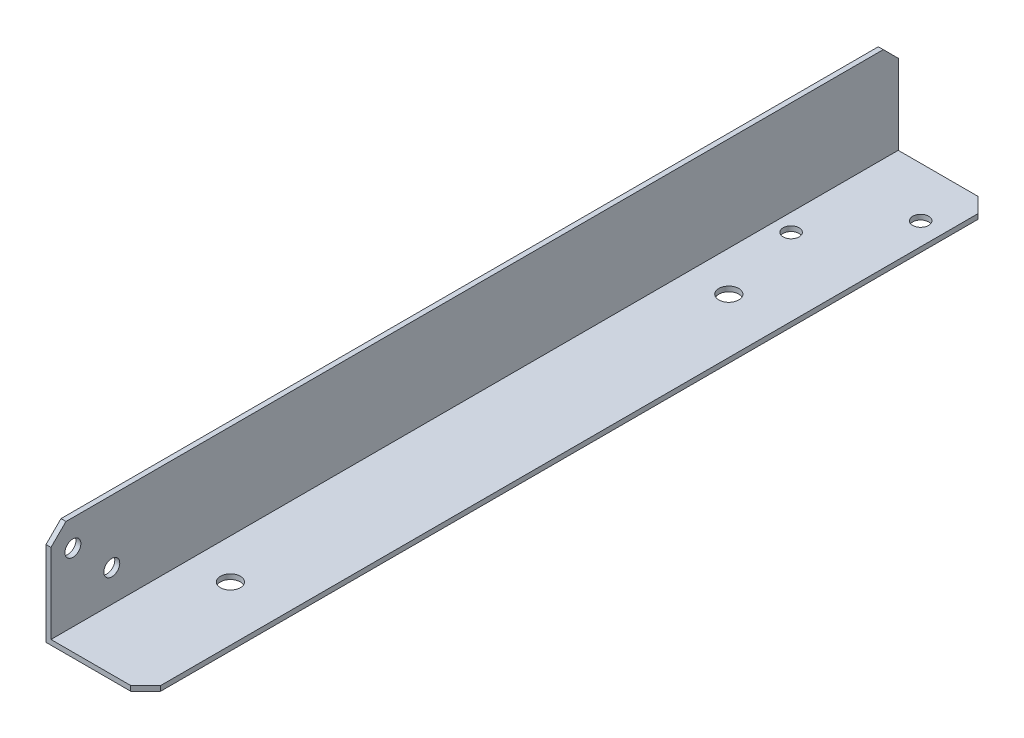
SolidWorks part; units mm, degrees
material "6063-T5"
ref_plane "Спереди" through (0, 0, 0) normal (0, 0, 1) x (1, 0, 0)
ref_plane "Сверху" through (0, 0, 0) normal (0, 1, 0) x (1, 0, 0)
ref_plane "Справа" through (0, 0, 0) normal (1, 0, 0) x (0, 0, -1)
sketch "Sketch1" plane through (0, 0, 0) normal (0, 0, 1) x (1, 0, 0)
  line L0 (0, 0) -> (20, 0)
  line L1 (20, 0) -> (20, 1)
  line L2 (20, 1) -> (1, 1)
  line L3 (1, 1) -> (1, 20)
  line L4 (1, 20) -> (0, 20)
  line L5 (0, 20) -> (0, 0)
  dimension "D1" = 20
  dimension "D2" = 20
  dimension "D3" = 1
  dimension "D4" = 1
extrude "Base" add sketch "Sketch1" along normal blind 170
chamfer "Chamfer1" distance 3 angle 45 4 edges at (20, 0.5, 170) (0.5, 20, 170) (0.5, 20, 0) (20, 0.5, 0)
hole_wizard "Ø4.0 (4) Cable tie Holes" positions "Sketch8" profile "Sketch9" hole size "Ø4.0" standard "ANSI Metric" end condition through all
sketch "Sketch8" plane through (0, 1, 0) normal (0, 1, 0) x (1, 0, 0)
  line L0 (0, -167) -> (0, -3) construction
  line L1 (17, 0) -> (1, 0) construction
  point P0 (9, -42)
  point P2 (9, -142)
  dimension "D1" = 9
  dimension "D2" = 42
  dimension "D3" = 142
sketch "Sketch9" plane through (9, 1, 42) normal (1, 0, 0) x (0, 0, 1)
  line L0 (0, 0) -> (0, 1)
  line L1 (0, 1) -> (2, 1)
  line L2 (2, 1) -> (2, 0)
  line L5 (2, 0) -> (0, 0)
  line L11 (0, -6.35) -> (0, 107.95) construction
  dimension "Thru Hole Dia." = 4
  dimension "Thru Hole Depth" = 1
hole_wizard "Ø3.1 (3.1) CableChainSideHoles" positions "Sketch10" profile "Sketch11" hole size "Ø3.2" standard "ANSI Metric" end condition through all
sketch "Sketch10" plane through (1, 0, 0) normal (1, 0, 0) x (0, 0, -1)
  line L0 (-167, 0) -> (-3, 0) construction
  line L1 (-170, 1) -> (-170, 17) construction
  point P0 (-165.6, 14.68)
  point P2 (-157.8, 7.38)
  dimension "D1" = 7.3
  dimension "D2" = 7.8
  dimension "D3" = 7.38
  dimension "D4" = 4.4
sketch "Sketch11" plane through (1, 14.68, 165.6) normal (0, 1, 0) x (0, 0, -1)
  line L0 (0, 0) -> (0, 1)
  line L1 (0, 1) -> (1.6, 1)
  line L2 (1.6, 1) -> (1.6, 0)
  line L5 (1.6, 0) -> (0, 0)
  line L11 (0, -6.35) -> (0, 107.95) construction
  dimension "Thru Hole Dia." = 3.2
  dimension "Thru Hole Depth" = 1
hole_wizard "Ø3.2 (3.2) CarriageSide" positions "Sketch12" profile "Sketch13" hole size "Ø3.2" standard "ANSI Metric" end condition through all
sketch "Sketch12" plane through (0, 1, 0) normal (0, 1, 0) x (1, 0, 0)
  line L0 (0, -167) -> (0, -3) construction
  line L1 (17, 0) -> (1, 0) construction
  point P0 (15.5, -10)
  point P2 (4.5, -25)
  dimension "D1" = 4.5
  dimension "D2" = 15
  dimension "D3" = 10
  dimension "D4" = 11
sketch "Sketch13" plane through (15.5, 1, 10) normal (1, 0, 0) x (0, 0, 1)
  line L0 (0, 0) -> (0, 1)
  line L1 (0, 1) -> (1.6, 1)
  line L2 (1.6, 1) -> (1.6, 0)
  line L5 (1.6, 0) -> (0, 0)
  line L11 (0, -6.35) -> (0, 107.95) construction
  dimension "Thru Hole Dia." = 3.2
  dimension "Thru Hole Depth" = 1
equation "\"D2@Sketch1\"=\"D1@Sketch1\""
equation "\"D4@Sketch1\"=\"D3@Sketch1\""
